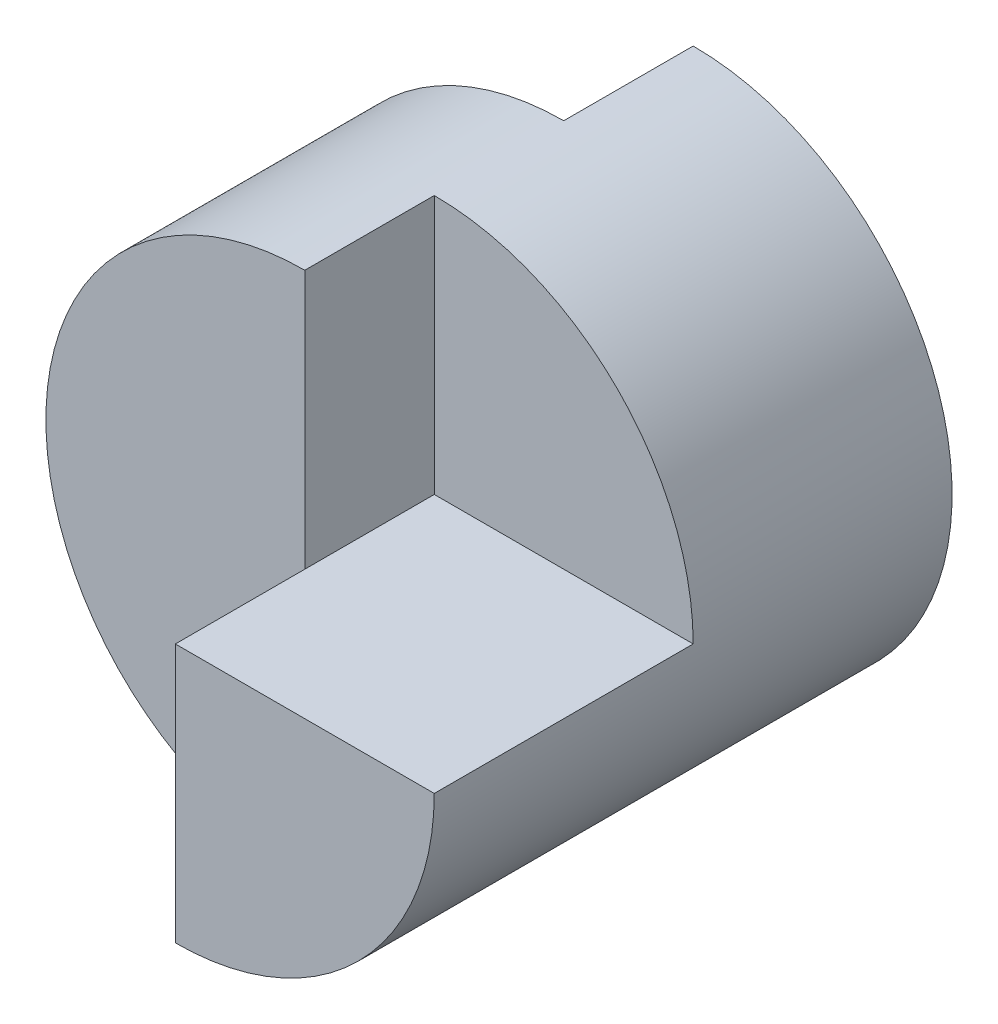
SolidWorks part; units mm, degrees
ref_plane "Front Plane" through (0, 0, 0) normal (0, 0, 1) x (1, 0, 0)
ref_plane "Top Plane" through (0, 0, 0) normal (0, 1, 0) x (1, 0, 0)
ref_plane "Right Plane" through (0, 0, 0) normal (1, 0, 0) x (0, 0, -1)
sketch "Sketch1" plane through (0, 0, 0) normal (0, 0, 1) x (1, 0, 0)
  circle A0 centre (0, 0) radius 20
  dimension "D1" = 40
extrude "Boss-Extrude1" add sketch "Sketch1" along normal blind 40
sketch "Sketch2" plane through (0, 0, 0) normal (0, 1, 0) x (1, 0, 0)
  line L1 (-20, 0) -> (0, 0)
  line L2 (-20, 0) -> (-20, -10)
  line L3 (-20, -10) -> (0, -10)
  line L4 (0, 0) -> (0, -10)
  line L5 (-20, -40) -> (0, -40)
  line L6 (-20, -40) -> (-20, -30)
  line L7 (-20, -30) -> (0, -30)
  line L8 (0, -40) -> (0, -30)
  dimension "D1" = 10
  dimension "D2" = 10
  dimension "D3" = 20
  dimension "D4" = 20
extrude "Cut-Extrude1" cut sketch "Sketch2" against normal blind 40 and the other way blind 40
sketch "Sketch3" plane through (0, 0, 40) normal (0, 0, 1) x (1, 0, 0)
  line L0 (0, 20) -> (0, -20) construction
  line L1 (0, 0) -> (20, 0)
  line L2 (0, 0) -> (0, 20)
  arc A0 (20, 0) -> (0, 20) centre (0, 0) ccw
  arc A1 (0, -20) -> (0, 20) centre (0, 0) ccw construction
extrude "Cut-Extrude2" cut sketch "Sketch3" against normal blind 20
